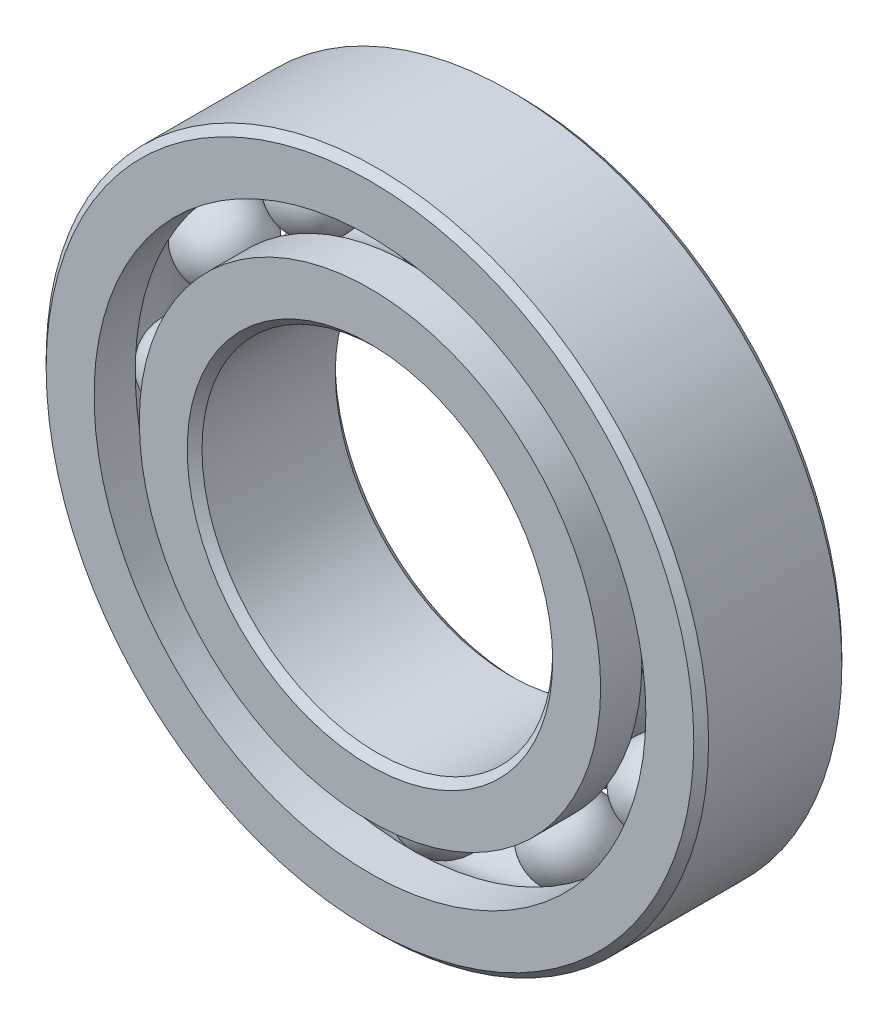
SolidWorks part; units mm, degrees
ref_plane "Front Plane" through (0, 0, 0) normal (0, 0, 1) x (1, 0, 0)
ref_plane "Top Plane" through (0, 0, 0) normal (0, 1, 0) x (1, 0, 0)
ref_plane "Right Plane" through (0, 0, 0) normal (1, 0, 0) x (0, 0, -1)
sketch "Sketch1" plane through (0, 0, 0) normal (1, 0, 0) x (0, 0, -1)
  line L0 (-9.5, 0) -> (9.5, 0) construction
  line L1 (0, 42.5) -> (0, -42.5) construction
  line L2 (8.55, 42.5) -> (-8.55, 42.5)
  line L3 (-8.55, 42.5) -> (-9.5, 41.55)
  line L4 (-9.5, 41.55) -> (-9.5, 35.4008)
  line L5 (-9.5, 35.4008) -> (-4.2222, 35.4008)
  line L6 (9.5, 35.4008) -> (4.2222, 35.4008)
  line L7 (9.5, 41.55) -> (9.5, 35.4008)
  line L8 (8.55, 42.5) -> (9.5, 41.55)
  line L9 (0, 42.5) -> (0, 32.4997) construction
  line L10 (0, 32.4997) -> (0, 22.4995) construction
  arc A0 (-4.2222, 35.4008) -> (4.2222, 35.4008) centre (0, 32.4997) cw
  point P14 (0, 22.4995)
  dimension "Width" = 19
  dimension "OD" = 85
  dimension "D1" = 45
  dimension "D2" = 0.95
  dimension "Shaft Dia" = 44.999
  dimension "D3" = 8.4444
  dimension "D4" = 2.9011
revolve "Revolve1" add sketch "Sketch1" angle 360 about L0
sketch "Sketch3" plane through (0, 0, 0) normal (1, 0, 0) x (0, 0, -1)
  line L0 (-9.5, 29.5987) -> (-4.2222, 29.5987)
  line L1 (0, 42.5) -> (0, -42.5) construction
  line L2 (-9.5, 41.55) -> (-9.5, 35.4008) construction
  line L3 (-9.5, 29.5987) -> (-9.5, 23.4495)
  line L4 (-8.55, 42.5) -> (-9.5, 41.55) construction
  line L5 (-9.5, 23.4495) -> (-8.55, 22.4995)
  line L6 (-8.55, 22.4995) -> (8.55, 22.4995)
  line L7 (8.55, 42.5) -> (8.55, -42.5) construction
  line L8 (8.55, 22.4995) -> (9.5, 23.4495)
  line L9 (9.5, -41.55) -> (9.5, 41.55) construction
  line L10 (9.5, 23.4495) -> (9.5, 29.5987)
  line L11 (9.5, 29.5987) -> (4.2222, 29.5987)
  line L13 (8.55, 42.5) -> (9.5, 41.55) construction
  arc A0 (4.2222, 35.4008) -> (-4.2222, 35.4008) centre (0, 32.4997) ccw construction
  arc A1 (4.2222, 29.5987) -> (-4.2222, 29.5987) centre (0, 32.4997) cw
revolve "Revolve3" add sketch "Sketch3" angle 360 about L0
sketch "Sketch4" plane through (0, 0, 0) normal (1, 0, 0) x (0, 0, -1)
  line L0 (-5.1228, 32.4997) -> (5.1228, 32.4997)
  arc A2 (-5.1228, 32.4997) -> (5.1228, 32.4997) centre (0, 32.4997) cw
  arc A3 (4.2222, 35.4008) -> (-4.2222, 35.4008) centre (0, 32.4997) ccw construction
revolve "Revolve4" add sketch "Sketch4" angle 360 about L0
ref_axis "Axis1" through (0, 0, -9.5) along (0, 0, 1)
pattern_circular "CirPattern1" count 12 every 30 about axis through (0, 0, -9.5) along (0, 0, 1) of bodies 104
sketch "Sketch5" plane through (0, 0, 0) normal (1, 0, 0) x (0, 0, -1)
  line L0 (-9.5, 35.4008) -> (-4.2222, 35.4008) construction
  line L1 (-9.025, 35.4008) -> (-5.1228, 35.4008)
  line L2 (-9.025, 35.4008) -> (-9.025, 29.5987)
  line L3 (-9.025, 29.5987) -> (-5.1228, 29.5987)
  line L4 (-5.1228, 35.4008) -> (-5.1228, 29.5987)
  line L5 (-9.5, 29.5987) -> (-4.2222, 29.5987) construction
  line L6 (9.5, 35.4008) -> (4.2222, 35.4008) construction
  line L7 (9.025, 35.4008) -> (5.1228, 35.4008)
  line L8 (9.025, 35.4008) -> (9.025, 29.5987)
  line L9 (9.025, 29.5987) -> (5.1228, 29.5987)
  line L10 (5.1228, 35.4008) -> (5.1228, 29.5987)
  line L11 (9.5, 29.5987) -> (4.2222, 29.5987) construction
  line L12 (-8.55, 42.5) -> (-9.5, 41.55) construction
  point P18 (-9.025, 42.025)
equation "\"D2@Sketch1\" = \"Width@Sketch1\"*.05"
equation "\"D3@Sketch1\" = \"Width@Sketch1\"/2.25"
equation "\"D4@Sketch1\" = (((\"OD@Sketch1\"-\"Width@Sketch1\")/2)/3.25)/3.5"
equation "\"D2@CirPattern1\" = 360/\"Balls@CirPattern1\""
